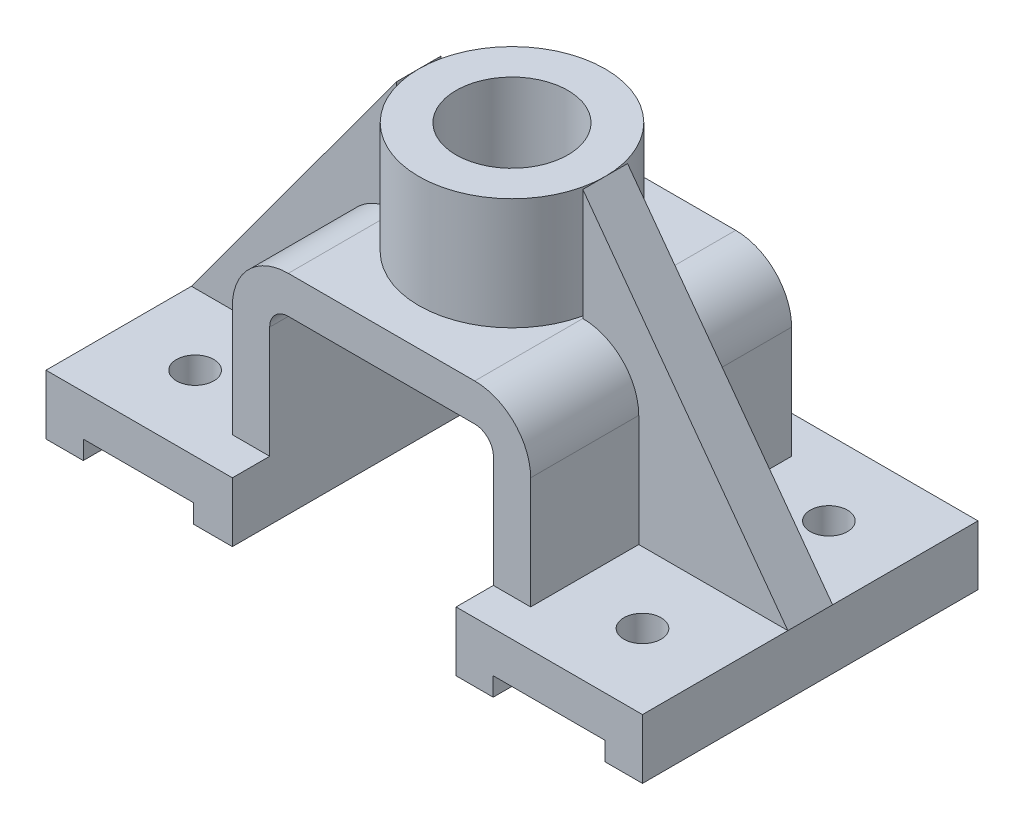
SolidWorks part; units mm, degrees
ref_plane "Front Plane" through (0, 0, 0) normal (0, 0, 1) x (1, 0, 0)
ref_plane "Top Plane" through (0, 0, 0) normal (0, 1, 0) x (1, 0, 0)
ref_plane "Right Plane" through (0, 0, 0) normal (1, 0, 0) x (0, 0, -1)
sketch "Sketch1" plane through (0, 0, 0) normal (0, 0, 1) x (1, 0, 0)
  line L0 (0, 0) -> (50, 0)
  line L1 (50, 0) -> (50, 16)
  line L2 (50, 16) -> (10, 16)
  line L3 (10, 16) -> (10, 61)
  line L4 (10, 61) -> (-70, 61)
  line L5 (-70, 61) -> (-70, 16)
  line L6 (-70, 16) -> (-110, 16)
  line L7 (-110, 16) -> (-110, 0)
  line L8 (-110, 0) -> (-60, 0)
  line L9 (-60, 0) -> (-60, 16)
  line L10 (-60, 16) -> (-60, 51)
  line L11 (-60, 51) -> (0, 51)
  line L12 (0, 51) -> (0, 3.8114)
  line L13 (0, 3.8114) -> (0, 0)
  dimension "D1" = 160
extrude "Boss-Extrude1" add sketch "Sketch1" along normal mid plane 90
ref_plane "Plane1" through (0, 0, 45) normal (0, 0, 1) x (1, 0, 0)
sketch "Sketch3" plane through (0, 0, 45) normal (0, 0, 1) x (1, 0, 0)
  line L0 (-110, 0) -> (-100, 0)
  line L1 (-110, 0) -> (-60, 0) construction
  line L2 (-100, 0) -> (-100, 5)
  line L3 (-100, 5) -> (-70.4916, 5)
  line L4 (-70.4916, 5) -> (-70.4916, 0)
  line L5 (50, 0) -> (40, 0)
  line L6 (0, 0) -> (50, 0) construction
  line L7 (40, 0) -> (40, 5)
  line L8 (40, 5) -> (9.9527, 5)
  line L9 (9.9527, 5) -> (9.9527, 0)
  line L10 (40, 0) -> (9.9527, 0)
  line L11 (-70.4916, 0) -> (-100, 0)
  dimension "D6" = 5
extrude "Cut-Extrude1" cut sketch "Sketch3" against normal through all contours L11 L4 L3 L2 | L7 L8 L9 L10 region at (-85.2458, 2.5, 45)
sketch "Sketch4" plane through (0, 0, 0) normal (1, 0, 0) x (0, 0, -1)
  line L0 (-45, 16) -> (-35, 16)
  line L1 (-45, 8.8) -> (-45, -8.8) construction
  line L2 (-45, 16) -> (45, 16) construction
  line L3 (-45, 16) -> (45, 16) construction
  line L4 (-35, 16) -> (-35, 61)
  line L5 (-45, 61) -> (45, 61) construction
  line L6 (-35, 61) -> (-45, 61)
  line L7 (-45, 61) -> (-45, 16)
  line L8 (45, 16) -> (35, 16)
  line L9 (35, 16) -> (35, 61)
  line L10 (35, 61) -> (45, 61)
  line L11 (45, 61) -> (45, 16)
  line L12 (45, 16) -> (35, 16)
  line L13 (35, 61) -> (45, 61)
  line L14 (-35, 16) -> (-45, 16)
  line L15 (-45, 61) -> (-35, 61)
extrude "Cut-Extrude2" cut sketch "Sketch4" against normal through all both and the other way through all contours L11 L10 L9 L8 | L6 L7 L0 L4 region at (0, 38.5, 40) region at (0, 38.5, -40)
sketch "Sketch6" plane through (0, 61, 0) normal (0, 1, 0) x (1, 0, 0)
  line L0 (-55, 0) -> (55, 0) construction
  circle A0 centre (-30, 0) radius 25
  dimension "D1" = 50
extrude "Boss-Extrude2" add sketch "Sketch6" along normal blind 30
sketch "Sketch7" plane through (0, 91, 0) normal (0, 1, 0) x (1, 0, 0)
  circle A0 centre (-30, 0) radius 15
  dimension "D1" = 30
extrude "Cut-Extrude4" cut sketch "Sketch7" against normal through all
fillet "Fillet1" radius 15 1 edges at (-70, 61, 0)
fillet "Fillet2" radius 5 1 edges at (-60, 51, 0)
fillet "Fillet3" radius 15 1 edges at (10, 61, 0)
fillet "Fillet4" radius 5 1 edges at (0, 51, 0)
sketch "Sketch12" plane through (0, 0, 0) normal (0, 0, 1) x (1, 0, 0)
  line L0 (-55, 91) -> (-110, 16)
  line L1 (50, 16) -> (0, 16) construction
  line L2 (10, 46) -> (10, 16) construction
  line L3 (-55, 91) -> (-55, 61) construction
  line L4 (-70, 16) -> (-70, 46) construction
  line L5 (-60, 16) -> (-110, 16) construction
  line L6 (50, 16) -> (10, 16)
  line L7 (10, 46) -> (10, 16)
  line L8 (-55, 91) -> (-55, 61)
  line L9 (-70, 16) -> (-70, 46)
  line L10 (-70, 16) -> (-110, 16)
  line L11 (-5, 91) -> (50, 16)
  line L12 (-5, 61) -> (-5, 91) construction
  line L13 (-5, 61) -> (-5, 91)
  arc A0 (10, 46) -> (-5, 61) centre (-5, 46) ccw construction
  arc A1 (-55, 61) -> (-70, 46) centre (-55, 46) ccw construction
  arc A2 (10, 46) -> (-5, 61) centre (-5, 46) ccw
  arc A3 (-55, 61) -> (-70, 46) centre (-55, 46) ccw
extrude "Boss-Extrude3" add sketch "Sketch12" along normal mid plane 12 separate body
sketch "Sketch16" plane through (0, 16, 0) normal (0, 1, 0) x (1, 0, 0)
  circle A0 centre (-90, 25) radius 5
  circle A1 centre (-90, -25) radius 5
  circle A2 centre (30, 25) radius 5
  circle A3 centre (30, -25) radius 5
  dimension "D9" = 10
extrude "Cut-Extrude5" cut sketch "Sketch16" against normal through all both and the other way through all
